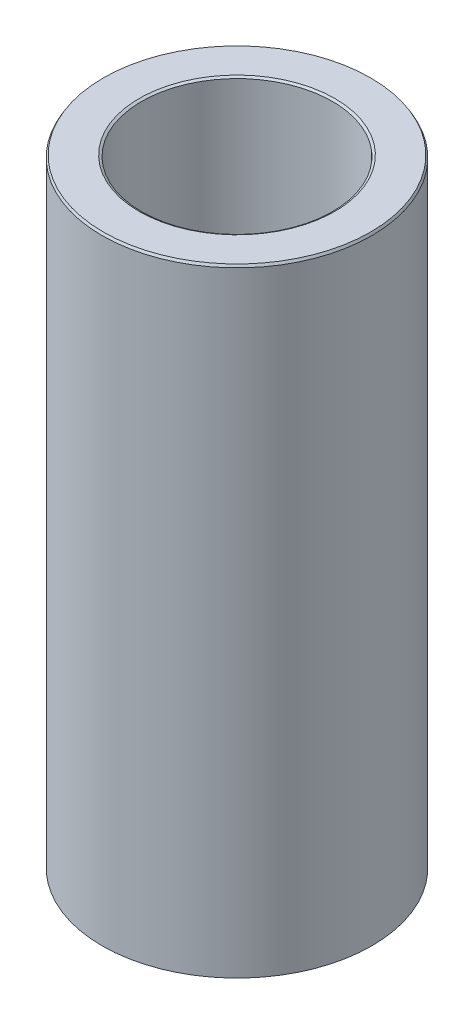
SolidWorks part; units mm, degrees
ref_plane "Front Plane" through (0, 0, 0) normal (0, 0, 1) x (1, 0, 0)
ref_plane "Top Plane" through (0, 0, 0) normal (0, 1, 0) x (1, 0, 0)
ref_plane "Right Plane" through (0, 0, 0) normal (1, 0, 0) x (0, 0, -1)
sketch "Sketch1" plane through (0, 0, 0) normal (0, 1, 0) x (1, 0, 0)
  circle A0 centre (0, 0) radius 60
  dimension "SLEEVE_OD" = 120
extrude "Boss-Extrude1" add sketch "Sketch1" along normal blind 275.1639
sketch "Sketch2" plane through (0, 0, 0) normal (0, 1, 0) x (1, 0, 0)
  circle A0 centre (0, 0) radius 42.4556
  dimension "BORE_D" = 84.9112
extrude "Cut-Extrude1" cut sketch "Sketch2" along normal through all
chamfer "Chamfer1" distance 1.0545 angle 30 4 edges at (0, 275.1639, 42.4556) (0, 0, 42.4556) (0, 0, 60) (0, 275.1639, 60) first distance on face at (0, 275.1639, 42.4556) first distance on face at (0, 0, 42.4556) first distance on face at (0, 275.1639, 60)
